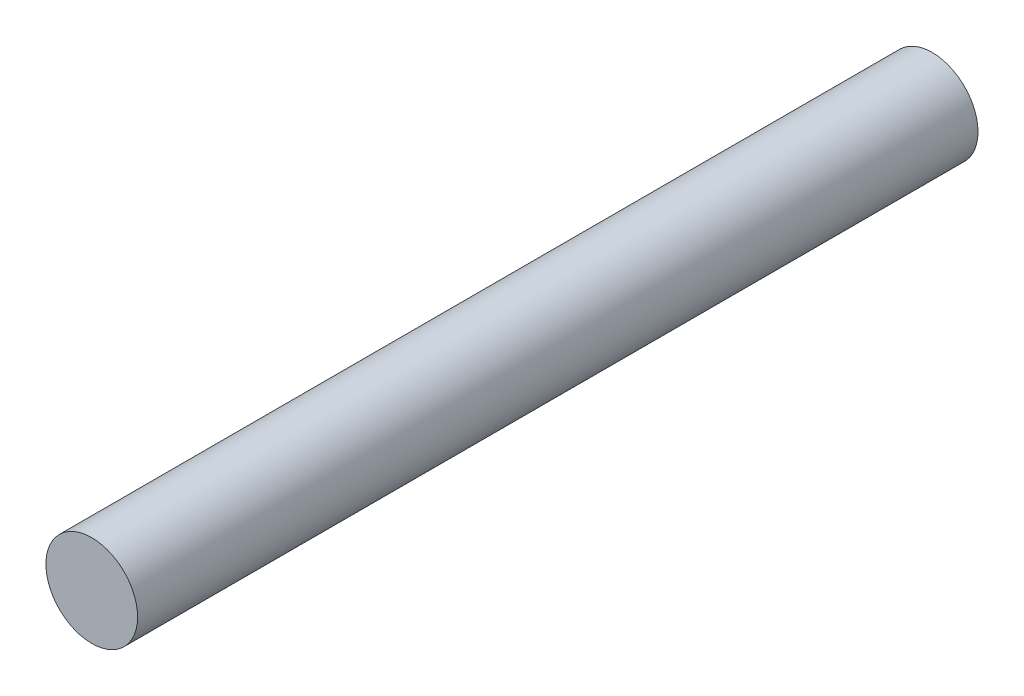
SolidWorks part; units mm, degrees
ref_plane "Alzado" through (0, 0, 0) normal (0, 0, 1) x (1, 0, 0)
ref_plane "Planta" through (0, 0, 0) normal (0, 1, 0) x (1, 0, 0)
ref_plane "Vista lateral" through (0, 0, 0) normal (1, 0, 0) x (0, 0, -1)
sketch "Croquis1" plane through (0, 0, 0) normal (0, 0, 1) x (1, 0, 0)
  circle A0 centre (0, 0) radius 3
  dimension "D1" = 6
extrude "Saliente-Extruir1" add sketch "Croquis1" along normal blind 55
